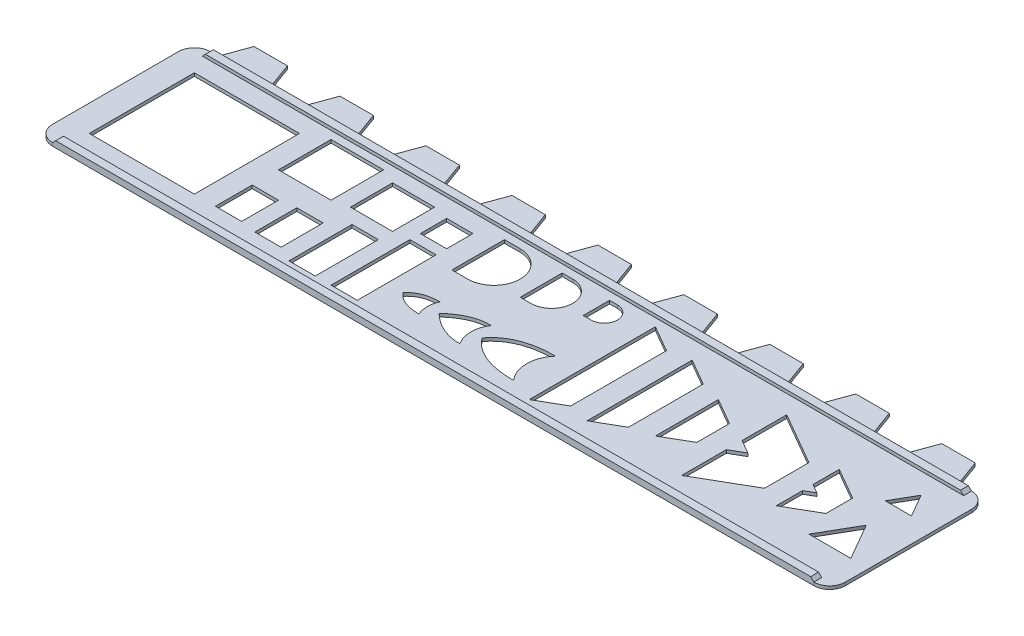
SolidWorks part; units mm, degrees
ref_plane "Front Plane" through (0, 0, 0) normal (0, 0, 1) x (1, 0, 0)
ref_plane "Top Plane" through (0, 0, 0) normal (0, 1, 0) x (1, 0, 0)
ref_plane "Right Plane" through (0, 0, 0) normal (1, 0, 0) x (0, 0, -1)
sketch "Sketch1" plane through (0, 0, 0) normal (0, 1, 0) x (1, 0, 0)
  line L1 (-80, 15) -> (80, 15)
  line L2 (-80, 15) -> (-80, -15)
  line L3 (-80, -15) -> (80, -15)
  line L4 (80, 15) -> (80, -15)
  line L5 (-80, 15) -> (80, -15) construction
  line L6 (-80, -15) -> (80, 15) construction
  point P0 (0, 0)
  dimension "D1" = 160
  dimension "D2" = 30
extrude "Boss-Extrude1" add sketch "Sketch1" along normal blind 0.6
sketch "Sketch2" plane through (0, 0.6, 0) normal (0, 1, 0) x (1, 0, 0)
  line L0 (80, 15) -> (-80, 15) construction
  line L1 (-75, -10) -> (-55, -10)
  line L2 (-75, -10) -> (-75, 10)
  line L3 (-75, 10) -> (-55, 10)
  line L4 (-55, -10) -> (-55, 10)
  line L5 (-75, -10) -> (-55, 10) construction
  line L6 (-75, 10) -> (-55, -10) construction
  line L7 (-5, 12) -> (-7, 12)
  line L8 (-80, 15) -> (-80, -15) construction
  line L9 (-80, -15) -> (80, -15) construction
  line L10 (-51, 12) -> (-41, 12)
  line L11 (-51, 12) -> (-51, 2)
  line L12 (-51, 2) -> (-41, 2)
  line L13 (-41, 12) -> (-41, 2)
  line L14 (-51, 12) -> (-41, 2) construction
  line L15 (-51, 2) -> (-41, 12) construction
  line L16 (-38, 10.7021) -> (-30, 10.7021)
  line L17 (-38, 10.7021) -> (-38, 2.7021)
  line L18 (-38, 2.7021) -> (-30, 2.7021)
  line L19 (-30, 10.7021) -> (-30, 2.7021)
  line L20 (-38, 10.7021) -> (-30, 2.7021) construction
  line L21 (-38, 2.7021) -> (-30, 10.7021) construction
  line L22 (-27, 10) -> (-22, 10)
  line L23 (-27, 10) -> (-27, 5)
  line L24 (-27, 5) -> (-22, 5)
  line L25 (-22, 10) -> (-22, 5)
  line L26 (-27, 10) -> (-22, 5) construction
  line L27 (-27, 5) -> (-22, 10) construction
  line L28 (-51, -3) -> (-46, -3)
  line L29 (-51, -3) -> (-51, -10)
  line L30 (-51, -10) -> (-46, -10)
  line L31 (-46, -3) -> (-46, -10)
  line L32 (-51, -3) -> (-46, -10) construction
  line L33 (-51, -10) -> (-46, -3) construction
  line L34 (-15, 12) -> (-18, 12)
  line L35 (-43, -2.5) -> (-38, -2.5)
  line L36 (-43, -2.5) -> (-43, -10.5)
  line L37 (-43, -10.5) -> (-38, -10.5)
  line L38 (-38, -2.5) -> (-38, -10.5)
  line L39 (-43, -2.5) -> (-38, -10.5) construction
  line L40 (-43, -10.5) -> (-38, -2.5) construction
  line L41 (-35, 0) -> (-30, 0)
  line L42 (-35, 0) -> (-35, -12)
  line L43 (-35, -12) -> (-30, -12)
  line L44 (-30, 0) -> (-30, -12)
  line L45 (-35, 0) -> (-30, -12) construction
  line L46 (-35, -12) -> (-30, 0) construction
  line L47 (-27, 3) -> (-22, 3)
  line L48 (-27, 3) -> (-27, -12)
  line L49 (-27, -12) -> (-22, -12)
  line L50 (-22, 3) -> (-22, -12)
  line L51 (-27, 3) -> (-22, -12) construction
  line L52 (-27, -12) -> (-22, 3) construction
  line L53 (-18, 12) -> (-18, 2)
  line L54 (-18, 2) -> (-15, 2)
  line L55 (-7, 12) -> (-7, 4)
  line L56 (-7, 4) -> (-5, 4)
  line L57 (3.5, 12) -> (2, 12)
  line L58 (2, 12) -> (2, 7)
  line L59 (2, 7) -> (3.5, 7)
  line L60 (6.0704, -2.3294) -> (-0.9283, -2.3137) construction
  line L61 (-0.9283, -2.3137) -> (-3.9296, -6.3294) construction
  line L62 (-3.9296, -6.3294) -> (10.6024, -6.3294) construction
  line L63 (6.0704, -10.3294) -> (-0.9283, -10.345) construction
  line L64 (-0.9283, -10.345) -> (-3.9296, -6.3294) construction
  line L65 (-12.0874, -6.3867) -> (-0.5555, -6.3867) construction
  line L66 (-5.0874, -3.3867) -> (-8.8163, -3.3176) construction
  line L67 (-8.8163, -3.3176) -> (-12.0874, -6.3867) construction
  line L68 (-5.0874, -9.3867) -> (-8.8163, -9.4558) construction
  line L69 (-8.8163, -9.4558) -> (-12.0874, -6.3867) construction
  line L70 (-18.8859, -6.3867) -> (-9.3539, -6.3867) construction
  line L71 (-13.8859, -4.3867) -> (-17.2992, -4.3789) construction
  line L72 (-17.2992, -4.3789) -> (-18.8859, -6.3867) construction
  line L73 (-13.8859, -8.3867) -> (-17.2992, -8.3946) construction
  line L74 (-17.2992, -8.3946) -> (-18.8859, -6.3867) construction
  arc A0 (-15, 2) -> (-15, 12) centre (-15, 7) ccw
  arc A1 (-5, 4) -> (-5, 12) centre (-5, 8) ccw
  arc A2 (3.5, 7) -> (3.5, 12) centre (3.5, 9.5) ccw
  arc A3 (6.0704, -2.3294) -> (6.0704, -10.3294) centre (10.6024, -6.3294) ccw
  arc A4 (-5.0874, -3.3867) -> (-5.0874, -9.3867) centre (-0.5555, -6.3867) ccw
  arc A5 (-13.8859, -4.3867) -> (-13.8859, -8.3867) centre (-9.3539, -6.3867) ccw
  spline S0 degree 2 poles (6.0704, -2.3294) (-0.9283, -2.3137) (-3.9296, -6.3294) knots 0 0 0 1 1 1
  spline S1 degree 2 poles (6.0704, -10.3294) (-0.9283, -10.345) (-3.9296, -6.3294) knots 0 0 0 1 1 1
  spline S2 degree 2 poles (-5.0874, -3.3867) (-8.8163, -3.3176) (-12.0874, -6.3867) knots 0 0 0 1 1 1
  spline S3 degree 2 poles (-5.0874, -9.3867) (-8.8163, -9.4558) (-12.0874, -6.3867) knots 0 0 0 1 1 1
  spline S4 degree 2 poles (-13.8859, -4.3867) (-17.2992, -4.3789) (-18.8859, -6.3867) knots 0 0 0 1 1 1
  spline S5 degree 2 poles (-13.8859, -8.3867) (-17.2992, -8.3946) (-18.8859, -6.3867) knots 0 0 0 1 1 1
  point P0 (-65, 0)
  point P7 (-34, 6.7021)
  point P10 (-46, 7)
  point P19 (-24.5, 7.5)
  point P24 (-48.5, -6.5)
  point P31 (-46, 2)
  point P32 (-40.5, -6.5)
  point P37 (-32.5, -6)
  point P42 (-24.5, -4.5)
  point P65 (-10, 7)
  point P66 (-1, 8)
  dimension "D1" = 20
  dimension "D2" = 5
  dimension "D3" = 5
  dimension "D4" = 10
  dimension "D5" = 10
  dimension "D6" = 3
  dimension "D7" = 8
  dimension "D8" = 8
  dimension "D9" = 5
  dimension "D10" = 5
  dimension "D11" = 4
  dimension "D12" = 3
  dimension "D13" = 3
  dimension "D14" = 5
  dimension "D15" = 5
  dimension "D16" = 5
  dimension "D17" = 4
  dimension "D18" = 5
  dimension "D19" = 8
  dimension "D20" = 0
  dimension "D21" = 3
  dimension "D22" = 12
  dimension "D23" = 5
  dimension "D24" = 3
  dimension "D25" = 3
  dimension "D26" = 5
  dimension "D27" = 15
  dimension "D28" = 3
  dimension "D29" = 5
  dimension "D30" = 10
  dimension "D31" = 3
  dimension "D32" = 8
  dimension "D33" = 2
  dimension "D34" = 5
  dimension "D35" = 1.5
  dimension "D36" = 3
  dimension "D37" = 3
  dimension "D38" = 3
  dimension "D39" = 4
  dimension "D40" = 3
  dimension "D41" = 3
  dimension "D42" = 8
  dimension "D43" = 6
  dimension "D44" = 4
  dimension "D45" = 10
  dimension "D46" = 5
  dimension "D47" = 7
  dimension "D48" = 3.1141
extrude "Cut-Extrude1" cut sketch "Sketch2" against normal blind 0.6
sketch "Sketch3" plane through (0, 0.6, 0) normal (0, 1, 0) x (1, 0, 0)
  line L0 (10.7176, 12) -> (10.7176, -12)
  line L1 (10.7176, -12) -> (15.7176, -9.1132)
  line L2 (15.7176, -9.1132) -> (15.7176, 9.1132)
  line L3 (15.7176, 9.1132) -> (10.7176, 12)
  line L4 (80, 15) -> (-80, 15) construction
  line L5 (-80, -15) -> (80, -15) construction
  line L6 (19.7176, 10) -> (19.7176, -10)
  line L7 (19.7176, -10) -> (24.7176, -7.1132)
  line L8 (24.7176, -7.1132) -> (24.7176, 7.1132)
  line L9 (24.7176, 7.1132) -> (19.7176, 10)
  line L10 (28.7176, 6) -> (28.7176, -6)
  line L11 (28.7176, -6) -> (33.7176, -3.1132)
  line L12 (33.7176, -3.1132) -> (33.7176, 3.1132)
  line L13 (33.7176, 3.1132) -> (28.7176, 6)
  dimension "D1" = 60
  dimension "D2" = 60
  dimension "D3" = 3
  dimension "D4" = 3
  dimension "D5" = 5
  dimension "D6" = 5
  dimension "D7" = 5
  dimension "D8" = 60
  dimension "D9" = 60
  dimension "D10" = 5
  dimension "D11" = 9
  dimension "D12" = 9
  dimension "D13" = 60
  dimension "D14" = 60
  dimension "D15" = 5
  dimension "D16" = 4
  dimension "D17" = 4
extrude "Cut-Extrude3" cut sketch "Sketch3" against normal blind 0.6
sketch "Sketch5" plane through (0, 0.6, 0) normal (0, 1, 0) x (1, 0, 0)
  line L0 (37.7176, 10) -> (37.7176, 1.5)
  line L1 (37.7176, -10) -> (47.7176, -4.2265)
  line L2 (47.7176, -4.2265) -> (47.7176, 4.2265)
  line L3 (47.7176, 4.2265) -> (37.7176, 10)
  line L4 (37.7176, 1.5) -> (40.3157, 0)
  line L5 (40.3157, 0) -> (37.7176, -1.5)
  line L6 (37.7176, -1.5) -> (37.7176, -10)
  line L7 (51.7176, 6) -> (51.7176, 1)
  line L8 (51.7176, -6) -> (57.7176, -2.5359)
  line L9 (57.7176, -2.5359) -> (57.7176, 2.5359)
  line L10 (57.7176, 2.5359) -> (51.7176, 6)
  line L11 (51.7176, 1) -> (53.4497, 0)
  line L12 (53.4497, 0) -> (51.7176, -1)
  line L13 (51.7176, -1) -> (51.7176, -6)
  line L14 (80, 15) -> (-80, 15) construction
  line L15 (33.7176, -3.1132) -> (33.7176, 3.1132) construction
  point P14 (57.7176, 0)
  point P17 (47.7176, 0)
  dimension "D1" = 60
  dimension "D2" = 60
  dimension "D3" = 10
  dimension "D4" = 20
  dimension "D5" = 60
  dimension "D6" = 60
  dimension "D7" = 60
  dimension "D8" = 3
  dimension "D9" = 60
  dimension "D10" = 6
  dimension "D11" = 12
  dimension "D12" = 60
  dimension "D13" = 60
  dimension "D14" = 2
  dimension "D15" = 0
  dimension "D16" = 5
  dimension "D17" = 9
  dimension "D18" = 0
  dimension "D19" = 4
  dimension "D20" = 4
extrude "Cut-Extrude4" cut sketch "Sketch5" against normal blind 0.6
sketch "Sketch6" plane through (0, 0.6, 0) normal (0, 1, 0) x (1, 0, 0)
  line L0 (63.759, 9.5191) -> (61.259, 5.189)
  line L1 (61.259, 5.189) -> (66.259, 5.189)
  line L2 (66.259, 5.189) -> (63.759, 9.5191)
  line L3 (63.485, -0.6397) -> (59.485, -7.5679)
  line L4 (59.485, -7.5679) -> (67.485, -7.5679)
  line L5 (67.485, -7.5679) -> (63.485, -0.6397)
  dimension "D1" = 5
  dimension "D2" = 5
  dimension "D3" = 5
  dimension "D4" = 8
  dimension "D5" = 8
  dimension "D6" = 8
extrude "Cut-Extrude5" cut sketch "Sketch6" against normal blind 0.6
sketch "Sketch7" plane through (0, 0.6, 0) normal (0, 1, 0) x (1, 0, 0)
  line L0 (80, 15) -> (-80, 15) construction
  line L1 (70.8769, 15) -> (80, 15)
  line L2 (70.8769, 15) -> (70.8769, -15)
  line L3 (70.8769, -15) -> (80, -15)
  line L4 (80, 15) -> (80, -15)
extrude "Cut-Extrude6" cut sketch "Sketch7" against normal blind 0.6
sketch "Sketch8" plane through (0, 0.6, 0) normal (0, 1, 0) x (1, 0, 0)
  line L0 (-75.4723, 15) -> (-73.6524, 20)
  line L1 (-73.6524, 20) -> (-67.2921, 20)
  line L2 (-67.2921, 20) -> (-65.4723, 15)
  line L3 (70.8769, 15) -> (-80, 15) construction
  line L4 (-65.4723, 15) -> (-75.4723, 15)
  line L5 (-59.1123, 15) -> (-57.2924, 20)
  line L6 (-57.2924, 20) -> (-50.9321, 20)
  line L7 (-50.9321, 20) -> (-49.1123, 15)
  line L8 (-49.1123, 15) -> (-59.1123, 15)
  line L9 (-42.7523, 15) -> (-40.9324, 20)
  line L10 (-40.9324, 20) -> (-34.5721, 20)
  line L11 (-34.5721, 20) -> (-32.7523, 15)
  line L12 (-32.7523, 15) -> (-42.7523, 15)
  line L13 (-26.3923, 15) -> (-24.5724, 20)
  line L14 (-24.5724, 20) -> (-18.2121, 20)
  line L15 (-18.2121, 20) -> (-16.3923, 15)
  line L16 (-16.3923, 15) -> (-26.3923, 15)
  line L17 (-10.0323, 15) -> (-8.2124, 20)
  line L18 (-8.2124, 20) -> (-1.8521, 20)
  line L19 (-1.8521, 20) -> (-0.0323, 15)
  line L20 (-0.0323, 15) -> (-10.0323, 15)
  line L21 (6.3277, 15) -> (8.1476, 20)
  line L22 (8.1476, 20) -> (14.5079, 20)
  line L23 (14.5079, 20) -> (16.3277, 15)
  line L24 (16.3277, 15) -> (6.3277, 15)
  line L25 (22.6877, 15) -> (24.5076, 20)
  line L26 (24.5076, 20) -> (30.8679, 20)
  line L27 (30.8679, 20) -> (32.6877, 15)
  line L28 (32.6877, 15) -> (22.6877, 15)
  line L29 (39.0477, 15) -> (40.8676, 20)
  line L30 (40.8676, 20) -> (47.2279, 20)
  line L31 (47.2279, 20) -> (49.0477, 15)
  line L32 (49.0477, 15) -> (39.0477, 15)
  line L33 (55.4077, 15) -> (57.2276, 20)
  line L34 (57.2276, 20) -> (63.5879, 20)
  line L35 (63.5879, 20) -> (65.4077, 15)
  line L36 (65.4077, 15) -> (55.4077, 15)
  line L41 (73.5876, 20) -> (79.9479, 20) [skipped]
  line L42 (81.7677, 15) -> (71.7677, 15) [skipped]
  line L43 (79.9479, 20) -> (81.7677, 15) [skipped]
  line L44 (71.7677, 15) -> (73.5876, 20) [skipped]
  dimension "D1" = 5
  dimension "D2" = 10
  dimension "D3" = 70
  dimension "D4" = 70
  dimension "D5" = 10
extrude "Boss-Extrude2" add sketch "Sketch8" against normal blind 0.6 separate body
fillet "Fillet1" radius 3 4 edges at (70.8769, 0.3, 15) (70.8769, 0.3, -15) (-80, 0.3, 15) (-80, 0.3, -15)
sketch "Sketch9" plane through (0, 0.6, 0) normal (0, 1, 0) x (1, 0, 0)
  line L1 (-77, 15) -> (67.8769, 15)
  line L2 (-77, 15) -> (-77, 13.5)
  line L3 (-77, 13.5) -> (67.8769, 13.5)
  line L4 (67.8769, 15) -> (67.8769, 13.5)
  line L5 (67.8769, -15) -> (-77, -15)
  line L6 (67.8769, -15) -> (67.8769, -13.5)
  line L7 (67.8769, -13.5) -> (-77, -13.5)
  line L8 (-77, -15) -> (-77, -13.5)
  dimension "D1" = 1.5
  dimension "D2" = 1.5
extrude "Boss-Extrude3" add sketch "Sketch9" along normal blind 0.6
chamfer "Chamfer1" distance 0.6 angle 45 4 edges at (67.8769, 1.2, 14.25) (67.8769, 1.2, -14.25) (-77, 1.2, 14.25) (-77, 1.2, -14.25)
